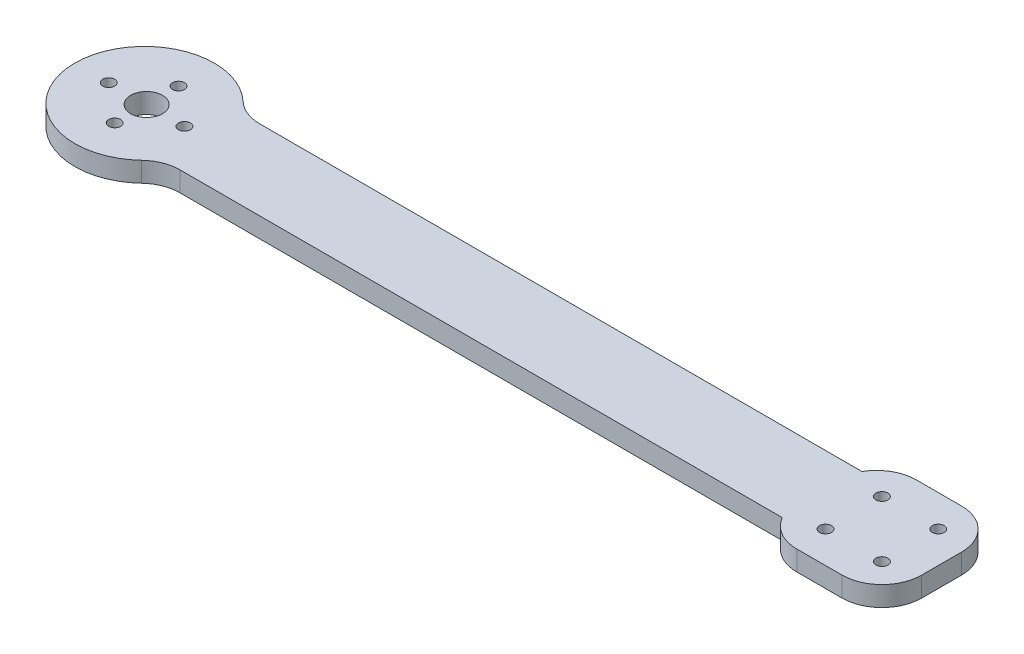
SolidWorks part; units mm, degrees
material "Thornel Mat VMA"
ref_plane "Front Plane" through (0, 0, 0) normal (0, 0, 1) x (1, 0, 0)
ref_plane "Top Plane" through (0, 0, 0) normal (0, 1, 0) x (1, 0, 0)
ref_plane "Right Plane" through (0, 0, 0) normal (1, 0, 0) x (0, 0, -1)
sketch "Sketch1" plane through (0, 0, 0) normal (0, 1, 0) x (1, 0, 0)
  line L0 (-100, 0) -> (100, 0) construction
  line L1 (70, 10) -> (75, 10) construction
  line L2 (-100, 10) -> (70, 10)
  line L3 (-100, 10) -> (-100, -10)
  line L4 (-100, -10) -> (70, -10)
  line L5 (100, 10) -> (100, -10)
  line L6 (-100, 10) -> (100, -10) construction
  line L7 (-100, -10) -> (94.4444, 9.4444) construction
  line L8 (70, 15) -> (100, 15)
  line L9 (70, 15) -> (70, 10)
  line L10 (70, -15) -> (100, -15)
  line L11 (100, 15) -> (100, -15)
  line L12 (70, 15) -> (100, -15) construction
  line L13 (70, -15) -> (100, 15) construction
  line L14 (95, 10) -> (100, 10) construction
  line L15 (75, 10) -> (95, 10) construction
  line L16 (94.4444, 9.4444) -> (100, 10) construction
  line L17 (70, -10) -> (75, -10) construction
  line L18 (95, -10) -> (100, -10) construction
  line L19 (75, -10) -> (95, -10) construction
  line L20 (70, 0) -> (70, -7) construction
  line L21 (70, -10) -> (70, -15)
  line L22 (70, 7) -> (70, 0) construction
  line L23 (70, 10) -> (70, 7) construction
  line L24 (70, -7) -> (70, -10) construction
  arc A0 (-85.6386, 10) -> (-85.6386, -10) centre (-100, 0) ccw
  arc A1 (-84.6855, -8.4686) -> (-82.5, 0) centre (-100, 0) ccw construction
  arc A2 (-82.5, 0) -> (-84.6855, 8.4686) centre (-100, 0) ccw construction
  arc A3 (-84.6855, 8.4686) -> (-85.6386, 10) centre (-100, 0) ccw construction
  arc A4 (-85.6386, -10) -> (-84.6855, -8.4686) centre (-100, 0) ccw construction
  point P3 (0, 0)
  point P4 (0, 0)
  point P10 (85, 0)
  dimension "D5" = 35
  dimension "D1" = 200
  dimension "D2" = 20
  dimension "D3" = 30
  dimension "D4" = 30
  dimension "D6" = 200
extrude "Boss-Extrude1" add sketch "Sketch1" along normal blind 5 contours L4 L21 L10 L11 L5 L8 L9 L2 L3 | L2 A0 L4 L3 region at (-104.3168, 0, 0) region at (5.9302, 0, 0)
sketch "Sketch2" plane through (0, 5, 0) normal (0, 1, 0) x (1, 0, 0)
  line L0 (-99.4856, 17.4924) -> (-99.4856, -17.4924) construction
  line L1 (-81.4712, 0) -> (-117.5, 0) construction
  circle A0 centre (-99.4856, 0) radius 4
  arc A1 (-85.6386, 10) -> (-85.6386, -10) centre (-100, 0) ccw construction
  circle A2 centre (-99.4856, 8) radius 1.5
  circle A3 centre (-99.4856, -8) radius 1.5
  circle A4 centre (-108.9856, 0) radius 1.5
  circle A5 centre (-89.9856, 0) radius 1.5
  point P9 (-99.4856, 0)
  point P11 (-99.4856, 0)
  dimension "D1" = 8
  dimension "D6" = 3
  dimension "D2" = 9.5
  dimension "D3" = 9.5
  dimension "D4" = 8
  dimension "D5" = 8
extrude "Cut-Extrude1" cut sketch "Sketch2" against normal blind 5
sketch "Sketch3" plane through (0, 5, 0) normal (0, 1, 0) x (1, 0, 0)
  line L0 (70, 15) -> (100, -15) construction
  circle A0 centre (85, 0) radius 10 construction
  circle A1 centre (77.9289, 7.0711) radius 1.5
  circle A2 centre (92.0711, 7.0711) radius 1.5
  circle A3 centre (92.0711, -7.0711) radius 1.5
  circle A4 centre (77.9289, -7.0711) radius 1.5
  point P17 (85, 0)
  dimension "D1" = 20
  dimension "D2" = 3
  dimension "D3" = 4
extrude "Cut-Extrude2" cut sketch "Sketch3" against normal blind 5
fillet "Fillet3" radius 10 4 edges at (70, 2.5, 15) (100, 2.5, 15) (100, 2.5, -15) (70, 2.5, -15)
fillet "Fillet4" radius 10 2 edges at (-85.6386, 2.5, -10) (-85.6386, 2.5, 10)
